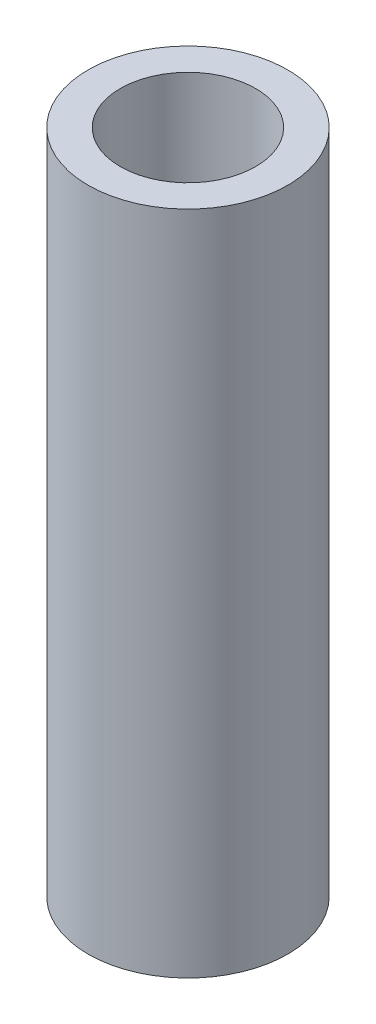
SolidWorks part; units mm, degrees
ref_plane "Front Plane" through (0, 0, 0) normal (0, 0, 1) x (1, 0, 0)
ref_plane "Top Plane" through (0, 0, 0) normal (0, 1, 0) x (1, 0, 0)
ref_plane "Right Plane" through (0, 0, 0) normal (1, 0, 0) x (0, 0, -1)
sketch "Sketch1" plane through (0, 0, 0) normal (0, 1, 0) x (1, 0, 0)
  circle A0 centre (0, 0) radius 4.5
  dimension "D1" = 9
extrude "Boss-Extrude1" add sketch "Sketch1" along normal blind 30
sketch "Sketch2" plane through (0, 30, 0) normal (0, 1, 0) x (1, 0, 0)
  circle A0 centre (0, 0) radius 3.05
  dimension "D1" = 6.1
extrude "Cut-Extrude1" cut sketch "Sketch2" against normal through all
